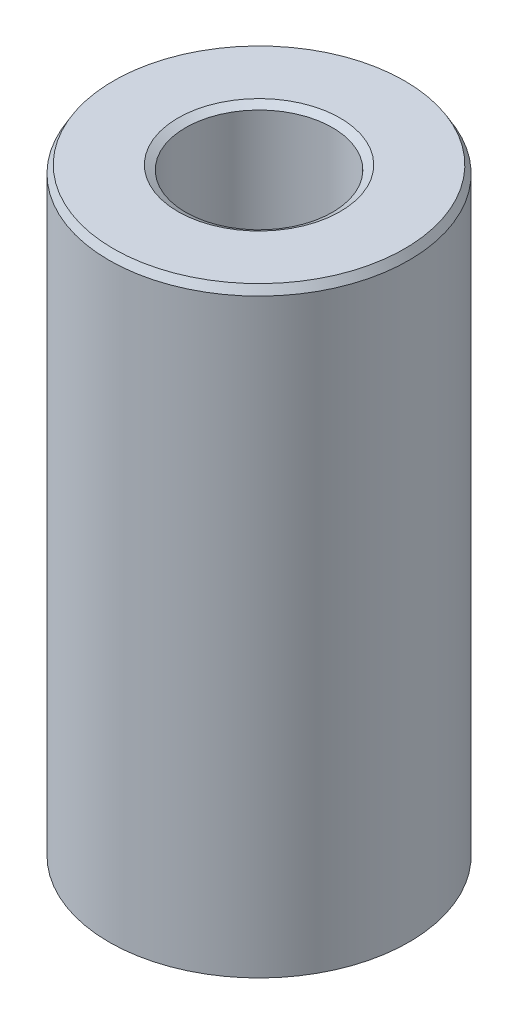
SolidWorks part; units mm, degrees
ref_plane "Front Plane" through (0, 0, 0) normal (0, 0, 1) x (1, 0, 0)
ref_plane "Top Plane" through (0, 0, 0) normal (0, 1, 0) x (1, 0, 0)
ref_plane "Right Plane" through (0, 0, 0) normal (1, 0, 0) x (0, 0, -1)
sketch "Sketch1" plane through (0, 0, 0) normal (0, 1, 0) x (1, 0, 0)
  circle A0 centre (0, 0) radius 45
  dimension "SLEEVE_OD" = 90
extrude "Boss-Extrude1" add sketch "Sketch1" along normal blind 180.8202
sketch "Sketch2" plane through (0, 0, 0) normal (0, 1, 0) x (1, 0, 0)
  circle A0 centre (0, 0) radius 22.0268
  dimension "BORE_D" = 44.0535
extrude "Cut-Extrude1" cut sketch "Sketch2" along normal through all
chamfer "Chamfer1" distance 2.3111 angle 30 4 edges at (0, 180.8202, 22.0268) (0, 0, 22.0268) (0, 0, 45) (0, 180.8202, 45) first distance on face at (0, 180.8202, 22.0268) first distance on face at (0, 0, 22.0268) first distance on face at (0, 180.8202, 45)
